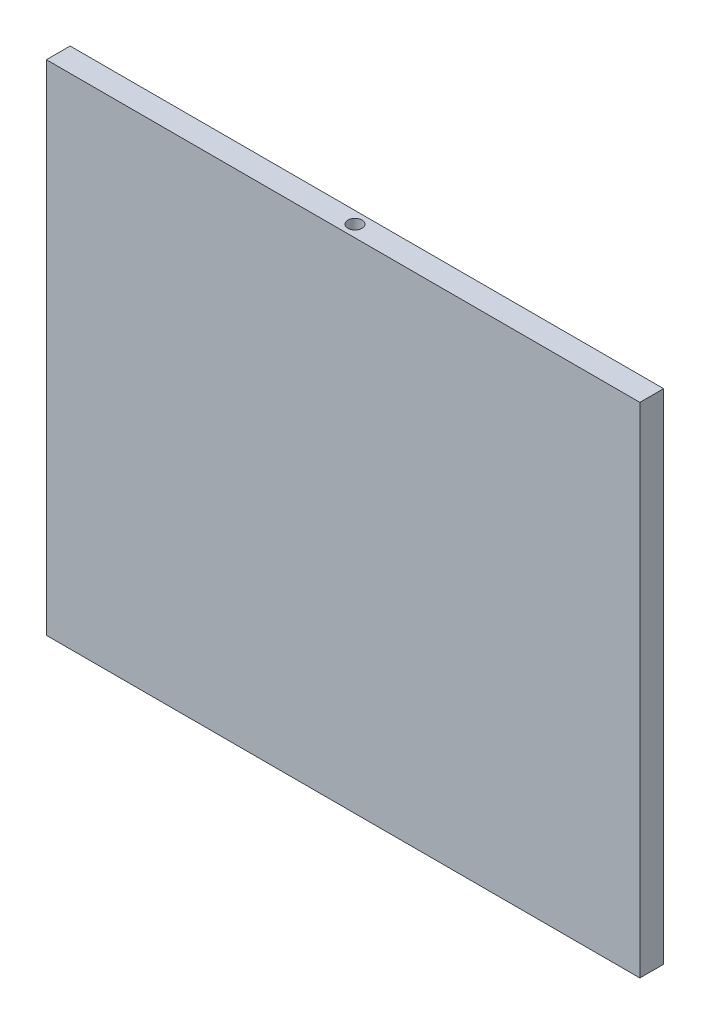
SolidWorks part; units mm, degrees
ref_plane "Plan de face" through (0, 0, 0) normal (0, 0, 1) x (1, 0, 0)
ref_plane "Plan de dessus" through (0, 0, 0) normal (0, 1, 0) x (1, 0, 0)
ref_plane "Plan de droite" through (0, 0, 0) normal (1, 0, 0) x (0, 0, -1)
sketch "Esquisse1" plane through (0, 0, 0) normal (0, 0, 1) x (1, 0, 0)
  line L1 (-125, -105) -> (125, -105)
  line L2 (-125, -105) -> (-125, 105)
  line L3 (-125, 105) -> (125, 105)
  line L4 (125, -105) -> (125, 105)
  line L5 (-125, -105) -> (125, 105) construction
  line L6 (-125, 105) -> (125, -105) construction
  point P0 (0, 0)
  dimension "D1" = 250
  dimension "D2" = 210
extrude "Boss.-Extru.1" add sketch "Esquisse1" along normal blind 10
sketch "Esquisse2" plane through (0, 105, 0) normal (0, 1, 0) x (1, 0, 0)
  line L0 (0, -10) -> (0, 0) construction
  line L1 (125, -10) -> (-125, -10) construction
  line L2 (125, 0) -> (-125, 0) construction
  circle A0 centre (0, -5) radius 3
  dimension "D1" = 6
extrude "Enlèv. mat.-Extru.1" cut sketch "Esquisse2" against normal through all both and the other way through all
